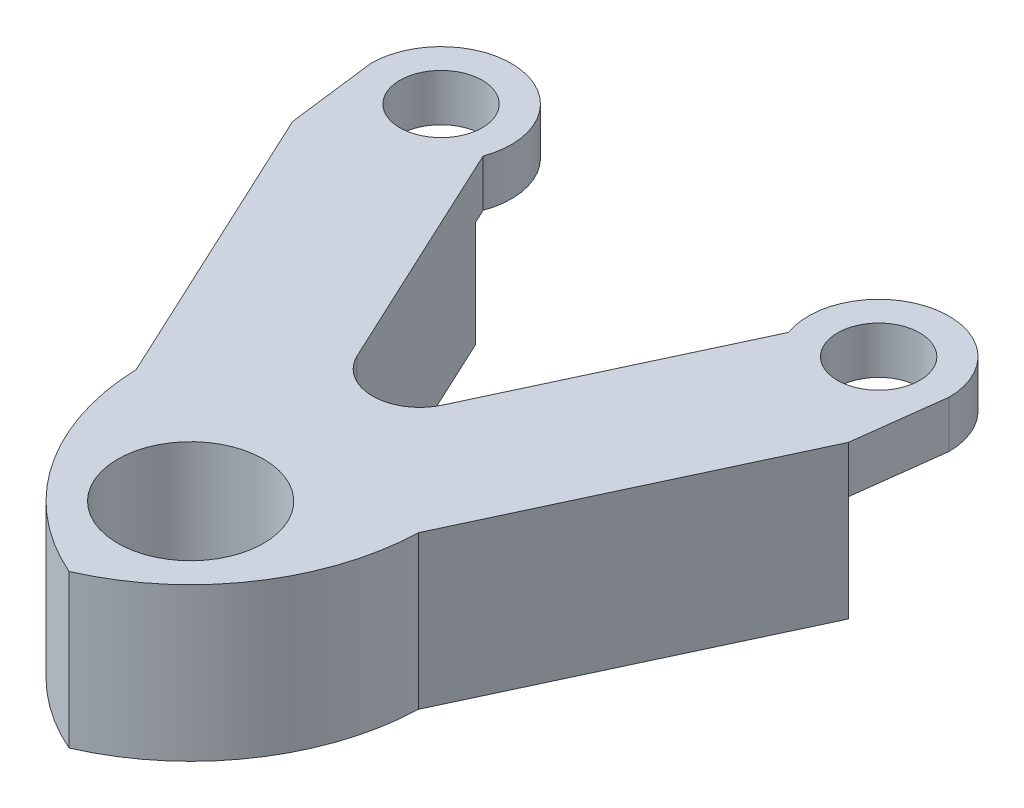
SolidWorks part; units mm, degrees
ref_plane "Front Plane" through (0, 0, 0) normal (0, 0, 1) x (1, 0, 0)
ref_plane "Top Plane" through (0, 0, 0) normal (0, 1, 0) x (1, 0, 0)
ref_plane "Right Plane" through (0, 0, 0) normal (1, 0, 0) x (0, 0, -1)
sketch "Sketch1" plane through (0, 0, 0) normal (0, 1, 0) x (1, 0, 0)
  line L1 (-6.4899, 18.9177) -> (0, 5)
  line L2 (-11.809, 16.1415) -> (-6, 3.684)
  line L5 (6.4899, 18.9177) -> (0, 5)
  line L6 (11.809, 16.1415) -> (6, 3.684)
  line L8 (0, -16.1983) -> (0, 16.1983) construction
  line L10 (-6, 3.684) -> (-6, -6)
  line L11 (-6, -6) -> (6, -6)
  line L12 (6, 3.684) -> (6, -6)
  arc A0 (11.809, 16.1415) -> (6.4899, 18.9177) centre (0, 0) ccw
  arc A2 (-6.4899, 18.9177) -> (-11.809, 16.1415) centre (0, 0) ccw
  point P10 (0, -6)
  point P17 (0, 0)
  dimension "D1" = 40
  dimension "D2" = 25
  dimension "D3" = 12
  dimension "D4" = 6
  dimension "D5" = 6
  dimension "D6" = 6
  dimension "D7" = 5
  dimension "D8" = 25
extrude "Boss-Extrude1" add sketch "Sketch1" along normal blind 6.5
sketch "Sketch2" plane through (0, 0, 0) normal (0, -1, 0) x (1, 0, 0)
  circle A0 centre (0, 0) radius 3.1
  dimension "D1" = 6.2
extrude "Cut-Extrude1" cut sketch "Sketch2" against normal through all
sketch "Sketch3" plane through (0, 6.5, 0) normal (0, 1, 0) x (1, 0, 0)
  line L0 (0, -28.2829) -> (0, 28.2829) construction
  line L1 (0, 0) -> (9.2976, 19.9388) construction
  line L2 (12.2852, 19.9388) -> (11.809, 16.1415)
  line L3 (11.809, 16.1415) -> (8.1523, 17.1795)
  line L4 (-11.809, 16.1415) -> (-8.1523, 17.1795)
  line L5 (-12.2852, 19.9388) -> (-11.809, 16.1415)
  circle A0 centre (9.2976, 19.9388) radius 1.75
  arc A2 (12.2852, 19.9388) -> (8.1523, 17.1795) centre (9.2976, 19.9388) ccw
  arc A3 (-12.2852, 19.9388) -> (-8.1523, 17.1795) centre (-9.2976, 19.9388) cw
  circle A4 centre (-9.2976, 19.9388) radius 1.75
  point P7 (0, 0)
  dimension "D1" = 3.5
  dimension "D2" = 22
  dimension "D3" = 25
  dimension "D4" = 3.8012
extrude "Boss-Extrude2" add sketch "Sketch3" against normal blind 2
sketch "Sketch5" plane through (0, 0, 0) normal (0, -1, 0) x (1, 0, 0)
  line L0 (0, -3.575) -> (0, 3.575) construction
  circle A0 centre (-9.2976, -19.9388) radius 3.5
  circle A1 centre (9.2976, -19.9388) radius 3.5
  arc M7 (-11.809, -16.1415) -> (-6.4899, -18.9177) centre (0, 0) ccw
  line M8 (-6.4899, -18.9177) -> (0, -5)
  line M9 (0, -5) -> (6.4899, -18.9177)
  arc M10 (6.4899, -18.9177) -> (11.809, -16.1415) centre (0, 0) ccw
  dimension "D1" = 7
extrude "Cut-Extrude2" cut sketch "Sketch5" along a picked direction on the side against the normal up to surface (4.5 mm away) contours A1 M9 M10 | A0 M8 M7
fillet "Fillet1" radius 10 2 edges at (6, 3.25, 6) (-6, 3.25, 6)
fillet "Fillet2" radius 2 1 edges at (0, 3.25, -5)
